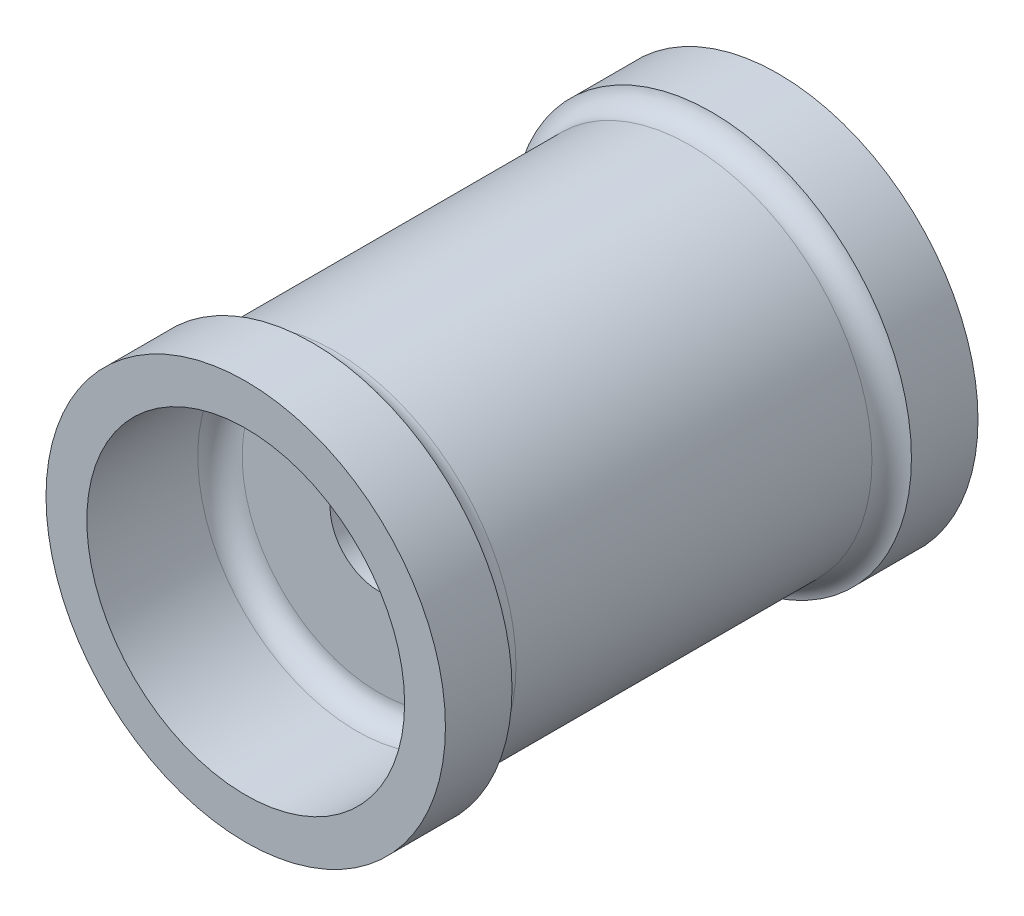
SolidWorks part; units mm, degrees
ref_plane "Płaszczyzna przednia" through (0, 0, 0) normal (0, 0, 1) x (1, 0, 0)
ref_plane "Płaszczyzna górna" through (0, 0, 0) normal (0, 1, 0) x (1, 0, 0)
ref_plane "Płaszczyzna prawa" through (0, 0, 0) normal (1, 0, 0) x (0, 0, -1)
sketch "Szkic1" plane through (0, 0, 0) normal (0, 0, 1) x (1, 0, 0)
  circle A0 centre (0, 0) radius 2.2
  circle A1 centre (0, 0) radius 8.2
extrude "Dodanie-wyciągnięcie6" add sketch "Szkic1" along normal blind 18
sketch "Szkic6" plane through (0, 0, 18) normal (0, 0, 1) x (1, 0, 0)
  circle A0 centre (0, 0) radius 2.2
  circle A1 centre (0, 0) radius 9
extrude "Dodanie-wyciągnięcie7" add sketch "Szkic6" along normal blind 3
sketch "Szkic7" plane through (0, 0, 0) normal (0, 0, -1) x (-1, 0, 0)
  circle A0 centre (0, 0) radius 2.2
  circle A1 centre (0, 0) radius 9
extrude "Dodanie-wyciągnięcie8" add sketch "Szkic7" along normal blind 3
sketch "Szkic8" plane through (0, 0, -3) normal (0, 0, -1) x (-1, 0, 0)
  circle A0 centre (0, 0) radius 7.16
extrude "Wytnij-wyciągnięcie2" cut sketch "Szkic8" against normal blind 6
sketch "Szkic9" plane through (0, 0, 21) normal (0, 0, 1) x (1, 0, 0)
  circle A0 centre (0, 0) radius 2.2
  circle A1 centre (0, 0) radius 7.16
  point P4 (10.6881, -2.371)
extrude "Wytnij-wyciągnięcie3" cut sketch "Szkic9" against normal blind 6
fillet "Zaokrąglenie2" radius 1 2 edges at (8.2, 0, 0) (8.2, 0, 18)
fillet "Zaokrąglenie3" radius 1 1 edges at (-7.16, 0, 3) type face fillet first side face at (-2.2, 0, 3) second side face at (-7.16, 0, 3)
fillet "Zaokrąglenie4" radius 1 1 edges at (7.16, 0, 15) type face fillet first side face at (2.2, 0, 15) second side face at (7.16, 0, 15)
